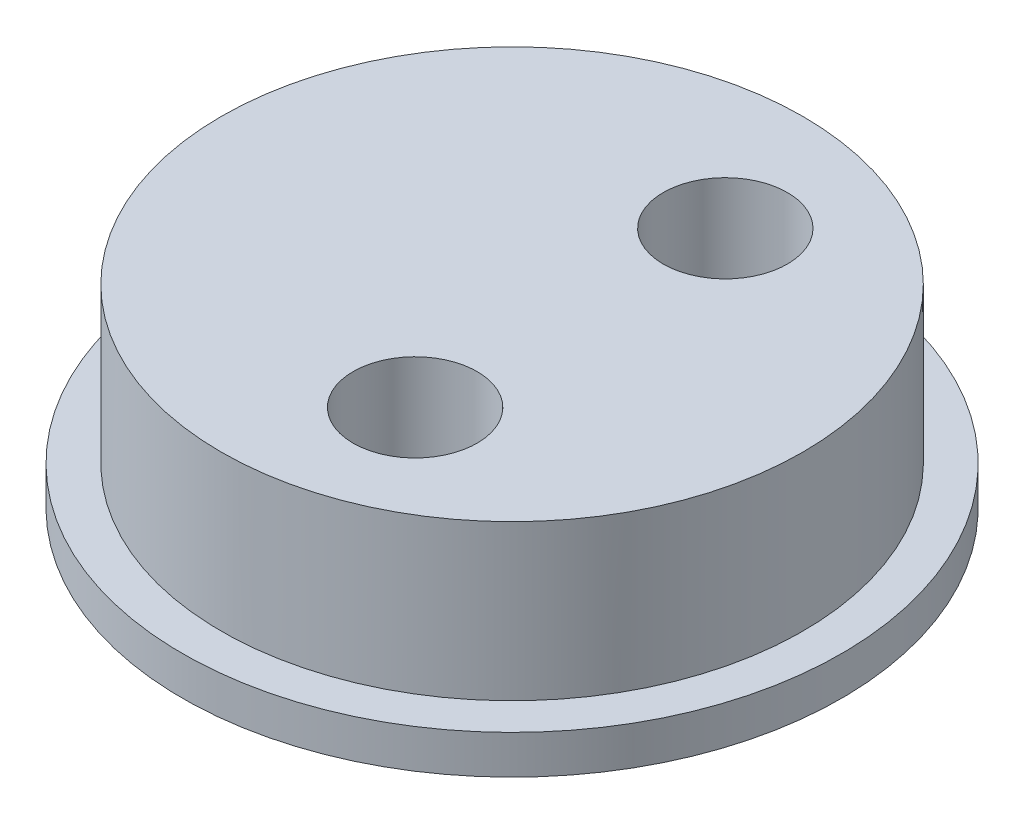
SolidWorks part; units mm, degrees
ref_plane "Front Plane" through (0, 0, 0) normal (0, 0, 1) x (1, 0, 0)
ref_plane "Top Plane" through (0, 0, 0) normal (0, 1, 0) x (1, 0, 0)
ref_plane "Right Plane" through (0, 0, 0) normal (1, 0, 0) x (0, 0, -1)
sketch "Sketch1" plane through (0, 0, 0) normal (0, 1, 0) x (1, 0, 0)
  line L0 (0, 0) -> (-1.5, 0) construction
  circle A1 centre (-1.5, 0) radius 7.5
  point P12 (0, 0)
  dimension "D3" = 15
  dimension "D2" = 1.5
extrude "Boss-Extrude1" add sketch "Sketch1" along normal blind 5
sketch "Sketch2" plane through (0, 0, 0) normal (0, -1, 0) x (1, 0, 0)
  line L0 (-12.8187, 0) -> (7.6603, 0) construction
  circle A0 centre (-1.5, 0) radius 8.5
  dimension "D2" = 17
  dimension "D1" = 1.5
extrude "Boss-Extrude2" add sketch "Sketch2" against normal blind 1
sketch "Sketch4" plane through (0, 5, 0) normal (0, 1, 0) x (1, 0, 0)
  line L0 (0, 8.8969) -> (0, -8.7328) construction
  circle A0 centre (0, 0) radius 4 construction
  circle A1 centre (0, 4) radius 1.6
  circle A2 centre (0, -4) radius 1.6
  dimension "D1" = 8
  dimension "D2" = 3.2
extrude "Cut-Extrude1" cut sketch "Sketch4" against normal through all
